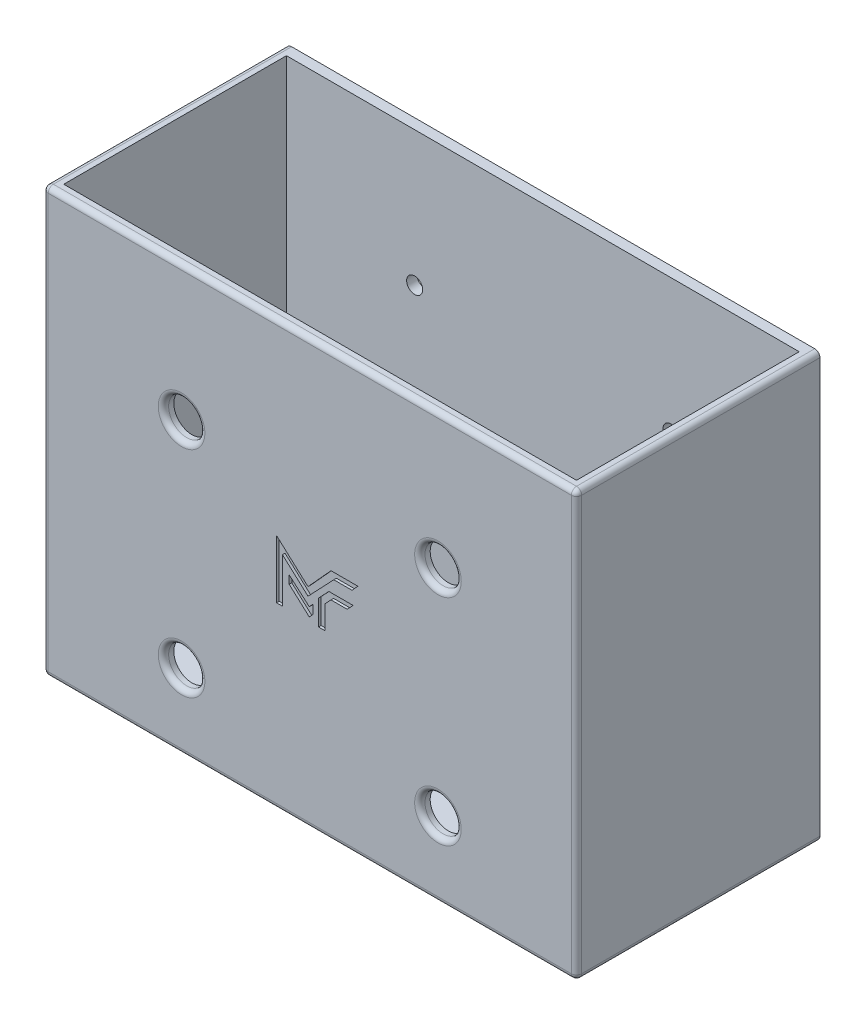
SolidWorks part; units mm, degrees
ref_plane "Plano frontal" through (0, 0, 0) normal (0, 0, 1) x (1, 0, 0)
ref_plane "Plano superior" through (0, 0, 0) normal (0, 1, 0) x (1, 0, 0)
ref_plane "Plano direito" through (0, 0, 0) normal (1, 0, 0) x (0, 0, -1)
sketch "Esboço1" plane through (0, 0, 0) normal (0, 1, 0) x (1, 0, 0)
  line L0 (-51.5, 0) -> (51.5, 0)
  line L1 (51.5, 0) -> (51.5, 47)
  line L2 (51.5, 47) -> (-51.5, 47)
  line L3 (-51.5, 47) -> (-51.5, 0)
  point P4 (0, 0)
  dimension "D1" = 103
  dimension "D2" = 47
extrude "Ressalto-extrusão1" add sketch "Esboço1" against normal blind 2
sketch "Esboço2" plane through (0, 0, 0) normal (0, 1, 0) x (1, 0, 0)
  line L0 (51.5, 47) -> (-51.5, 47) construction
  line L1 (51.5, 47) -> (-51.5, 47)
  line L2 (-51.5, 47) -> (-51.5, 0) construction
  line L3 (-51.5, 47) -> (-51.5, 0)
  line L4 (51.5, 0) -> (51.5, 47) construction
  line L5 (-51.5, 0) -> (51.5, 0) construction
  line L6 (51.5, 0) -> (51.5, 47)
  line L7 (-51.5, 0) -> (51.5, 0)
  line L8 (49.5, 45) -> (-49.5, 45)
  line L9 (-49.5, 45) -> (-49.5, 2)
  line L10 (-49.5, 2) -> (49.5, 2)
  line L11 (49.5, 2) -> (49.5, 45)
  dimension "D1" = 2
extrude "Ressalto-extrusão2" add sketch "Esboço2" along normal blind 80
sketch "Esboço3" plane through (0, 0, -45) normal (0, 0, 1) x (1, 0, 0)
  line L0 (-49.5, 28) -> (49.5, 28)
  line L1 (-49.5, 80) -> (-49.5, 0) construction
  line L2 (49.5, 80) -> (49.5, 0) construction
  line L3 (49.5, 0) -> (-49.5, 0) construction
  line L4 (-49.5, 25) -> (49.5, 25)
  line L5 (-49.5, 28) -> (-49.5, 25)
  line L6 (49.5, 28) -> (49.5, 25)
  dimension "D1" = 28
  dimension "D2" = 3
extrude "Ressalto-extrusão3" add sketch "Esboço3" along normal blind 3
fillet "Filete1" radius 5 1 edges at (0, 25, -45)
sketch "Esboço4" plane through (0, 0, -45) normal (0, 0, 1) x (1, 0, 0)
  line L0 (0, 25) -> (0, 0) construction
  line L1 (-49.5, 25) -> (49.5, 25) construction
  line L2 (0, 12.5) -> (49.5, 12.5) construction
  line L3 (49.5, 20.4174) -> (49.5, 0) construction
  line L4 (0, 28) -> (0, 80) construction
  line L5 (49.5, 28) -> (-49.5, 28) construction
  line L6 (49.5, 80) -> (-49.5, 80) construction
  line L7 (0, 54) -> (49.5, 54) construction
  line L8 (49.5, 20.4174) -> (-49.5, 20.4174) construction
  circle A0 centre (24.75, 12.5) radius 1.55
  circle A1 centre (24.75, 54) radius 1.55
  circle A2 centre (-24.75, 12.5) radius 1.55
  circle A3 centre (-24.75, 54) radius 1.55
  dimension "D1" = 3.1
  dimension "D2" = 24.75
extrude "Corte-extrusão1" cut sketch "Esboço4" against normal blind 3
sketch "Esboço5" plane through (0, 0, 0) normal (0, 0, 1) x (1, 0, 0)
  circle A0 centre (-24.75, 54) radius 3.5
  circle A1 centre (24.75, 54) radius 3.5
  circle A2 centre (-24.75, 12.5) radius 3.5
  circle A3 centre (24.75, 12.5) radius 3.5
  dimension "D1" = 7
extrude "Corte-extrusão2" cut sketch "Esboço5" against normal blind 3
fillet "Filete2" radius 1 4 edges at (28.25, 12.5, 0) (-21.25, 12.5, 0) (28.25, 54, 0) (-21.25, 54, 0)
fillet "Filete3" radius 1 8 edges at (-51.5, 80, -23.5) (0, 80, 0) (51.5, 80, -23.5) (51.5, -2, -23.5) (0, -2, 0) (-51.5, -2, -23.5) (-51.5, 39, 0) (51.5, 39, 0)
sketch "Esboço6" plane through (0, -2, 0) normal (0, -1, 0) x (1, 0, 0)
  line L0 (0, 0) -> (0, -47) construction
  line L1 (50.5, -47) -> (-50.5, -47) construction
  line L2 (0, -23.5) -> (51.5, -23.5) construction
  line L3 (51.5, -1) -> (51.5, -47) construction
  line L4 (21.75, -23.5) -> (29.75, -23.5) construction
  line L5 (21.75, -17.5) -> (29.75, -17.5)
  line L6 (21.75, -29.5) -> (29.75, -29.5)
  line L7 (-21.75, -23.5) -> (-29.75, -23.5) construction
  line L8 (-21.75, -17.5) -> (-29.75, -17.5)
  line L9 (-21.75, -29.5) -> (-29.75, -29.5)
  arc A0 (21.75, -17.5) -> (21.75, -29.5) centre (21.75, -23.5) ccw
  arc A1 (29.75, -29.5) -> (29.75, -17.5) centre (29.75, -23.5) ccw
  arc A2 (-21.75, -17.5) -> (-21.75, -29.5) centre (-21.75, -23.5) cw
  arc A3 (-29.75, -29.5) -> (-29.75, -17.5) centre (-29.75, -23.5) cw
  point P11 (25.75, -23.5)
  point P16 (0, 0)
  point P19 (-25.75, -23.5)
  point P24 (25.75, -23.5)
  dimension "D1" = 6
  dimension "D3" = 8
extrude "Corte-extrusão3" cut sketch "Esboço6" against normal blind 3
fillet "Filete4" radius 1 16 edges at (25.75, -2, -17.5) (35.75, -2, -23.5) (25.75, -2, -29.5) (-25.75, -2, -17.5) (-15.75, -2, -23.5) (-25.75, -2, -29.5) (15.75, -2, -23.5) (-35.75, -2, -23.5) (15.75, 0, -23.5) (25.75, 0, -29.5) (35.75, 0, -23.5) (-35.75, 0, -23.5) (-25.75, 0, -29.5) (-15.75, 0, -23.5) (25.75, 0, -17.5) (-25.75, 0, -17.5)
sketch "Esboço7" plane through (0, -2, 0) normal (0, -1, 0) x (1, 0, 0)
  line L0 (0, -12.5) -> (51.5, -12.5) construction
  line L4 (0, 0) -> (0, -47) construction
  line L5 (50.5, -47) -> (-50.5, -47) construction
  line L6 (51.5, -1) -> (51.5, -47) construction
  line L7 (0, -12.5) -> (-51.5, -12.5) construction
  line L8 (-51.5, -47) -> (-51.5, -1) construction
  line L9 (29.75, -17.5) -> (21.75, -17.5) construction
  text T0 "<b> AC</b>"
  text T1 "<b>DC</b>"
  dimension "D1" = 5
extrude "Corte-extrusão4" cut sketch "Esboço7" against normal blind 0.5
sketch "Logo_MF" plane through (0, 0, 0) normal (0, 0, 1) x (1, 0, 0)
  line L0 (-6.4127, 32.5654) -> (-5.2791, 32.5654)
  line L1 (-5.2791, 32.5654) -> (-5.2791, 41.1853)
  line L2 (-5.2791, 41.1853) -> (-0.3401, 36.6988)
  line L3 (-0.3401, 36.6988) -> (4.643, 41.9417)
  line L4 (4.643, 41.9417) -> (8.1619, 41.9417)
  line L5 (8.1619, 41.9417) -> (9.2898, 43.1834)
  line L6 (9.2898, 43.1834) -> (4.0993, 43.1834)
  line L7 (4.0993, 43.1834) -> (-0.3383, 38.2983)
  line L8 (-0.3383, 38.2983) -> (-6.4127, 43.8161)
  line L9 (-6.4127, 43.8161) -> (-6.4127, 32.5654)
  line L10 (-3.9704, 38.4461) -> (-3.9704, 36.8756)
  line L11 (-3.9704, 36.8756) -> (-0.09, 33.3507)
  line L12 (-0.09, 33.3507) -> (0.5909, 34.1003)
  line L13 (0.5909, 34.1003) -> (0.5909, 35.8204)
  line L14 (0.5909, 35.8204) -> (-0.0911, 35.0696)
  line L15 (-0.0911, 35.0696) -> (-3.9704, 38.4461)
  line L16 (1.6909, 32.5654) -> (1.6909, 37.4075)
  line L17 (1.6909, 37.4075) -> (3.6909, 39.5117)
  line L18 (3.6909, 39.5117) -> (8.3744, 39.5117)
  line L19 (8.3744, 39.5117) -> (7.222, 38.2992)
  line L20 (7.222, 38.2992) -> (4.0998, 38.2992)
  line L21 (4.0998, 38.2992) -> (2.906, 37.0431)
  line L22 (2.906, 37.0431) -> (2.906, 32.5654)
  line L23 (2.906, 32.5654) -> (1.6909, 32.5654)
  line L24 (50.5, -1) -> (50.5, 79) construction
  line L25 (50.5, 79) -> (-50.5, 79) construction
  dimension "D1" = 2.43
  dimension "D2" = 6.97
  dimension "D3" = 1.1
  dimension "D4" = 41.2102
  dimension "D5" = 42.1256
  dimension "D6" = 42.3381
  dimension "D7" = 43.278
  dimension "D8" = 45.857
  dimension "D9" = 46.4002
  dimension "D10" = 46.4007
  dimension "D11" = 46.8091
  dimension "D12" = 47.594
  dimension "D13" = 48.8091
  dimension "D14" = 54.4704
  dimension "D15" = 50.59
  dimension "D16" = 50.5911
  dimension "D17" = 50.8383
  dimension "D18" = 50.8401
  dimension "D19" = 56.9127
  dimension "D20" = 35.1839
  dimension "D21" = 35.8166
  dimension "D22" = 37.8147
  dimension "D23" = 40.5539
  dimension "D24" = 42.1244
  dimension "D25" = 43.1796
  dimension "D26" = 46.4346
extrude "Corte-extrusão5" cut sketch "Logo_MF" against normal blind 0.5
